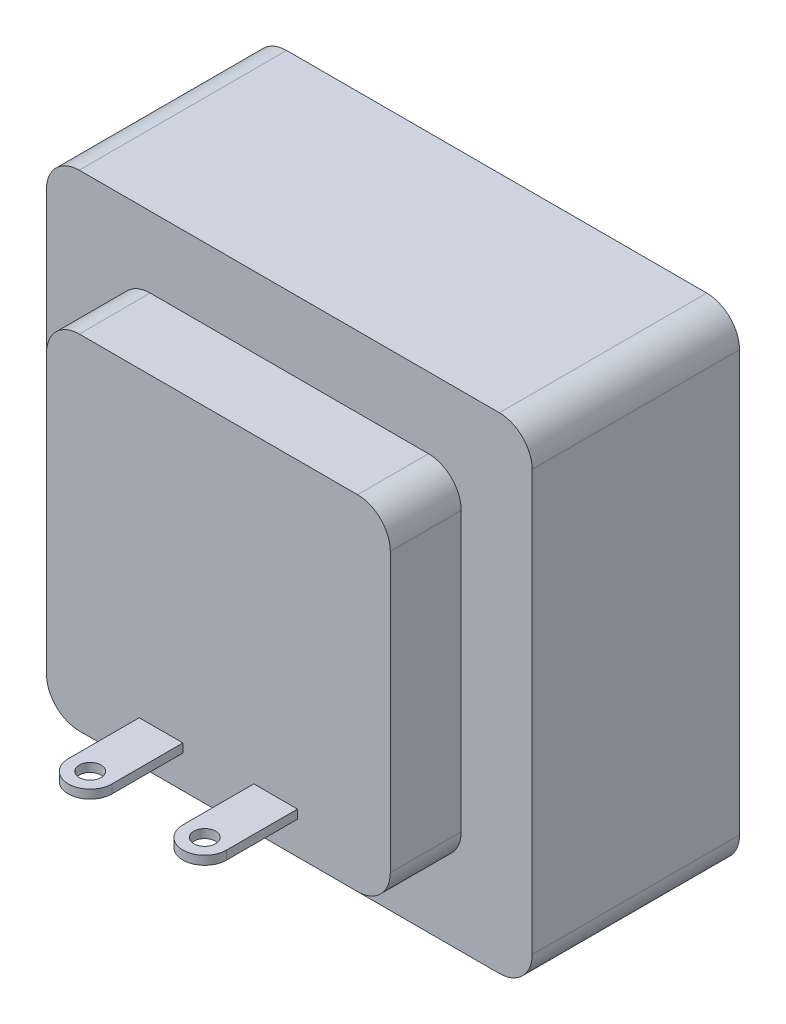
SolidWorks part; units mm, degrees
ref_plane "Front" through (0, 0, 0) normal (0, 0, 1) x (1, 0, 0)
ref_plane "Top" through (0, 0, 0) normal (0, 1, 0) x (1, 0, 0)
ref_plane "Right" through (0, 0, 0) normal (1, 0, 0) x (0, 0, -1)
sketch "Sketch1" plane through (0, 0, 0) normal (0, 0, 1) x (1, 0, 0)
  line L0 (22.25, -22.25) -> (-22.25, 22.25) construction
  line L1 (-22.25, 22.25) -> (22.25, 22.25)
  line L2 (-22.25, 22.25) -> (-22.25, -22.25)
  line L3 (-22.25, -22.25) -> (22.25, -22.25)
  line L4 (22.25, 22.25) -> (22.25, -22.25)
  dimension "D1" = 44.5
  dimension "D2" = 44.5
extrude "Base-Extrude" add sketch "Sketch1" along normal mid plane 19
sketch "Sketch2" plane through (0, 0, 0) normal (1, 0, 0) x (0, 0, -1)
  line L0 (-16, -15.75) -> (16, 15.75) construction
  line L1 (-16, 15.75) -> (16, 15.75)
  line L2 (-16, 15.75) -> (-16, -15.75)
  line L3 (-16, -15.75) -> (16, -15.75)
  line L4 (16, 15.75) -> (16, -15.75)
  line L5 (-9.5, 22.25) -> (9.5, 22.25) construction
  dimension "D1" = 6.5
  dimension "D2" = 32
extrude "Boss-Extrude1" add sketch "Sketch2" along normal offset from surface 6.5 and the other way offset from surface 6.5 up to face at (22.25, 0, 0) other way up to face at (-22.25, 0, 0)
fillet "Fillet1" radius 3 12 edges at (15.75, 15.75, 12.75) (22.25, 22.25, 0) (15.75, 15.75, -12.75) (-15.75, -15.75, -12.75) (-15.75, -15.75, 12.75) (15.75, -15.75, -12.75) (15.75, -15.75, 12.75) (-15.75, 15.75, -12.75) (-22.25, 22.25, 0) (-15.75, 15.75, 12.75) (-22.25, -22.25, 0) (22.25, -22.25, 0)
sketch "Sketch3" plane through (0, 0, 16) normal (0, 0, 1) x (1, 0, 0)
  line L0 (0, 0) -> (0, -20.3808) construction
  line L1 (-7.25, -12.75) -> (-3.25, -12.75)
  line L2 (-7.25, -12.75) -> (-7.25, -11.95)
  line L3 (-7.25, -11.95) -> (-3.25, -11.95)
  line L4 (-3.25, -12.75) -> (-3.25, -11.95)
  line L5 (3.25, -12.75) -> (3.25, -11.95)
  line L6 (7.25, -11.95) -> (3.25, -11.95)
  line L7 (7.25, -12.75) -> (7.25, -11.95)
  line L8 (7.25, -12.75) -> (3.25, -12.75)
  line L9 (12.75, -15.75) -> (-12.75, -15.75) construction
  dimension "D1" = 4
  dimension "D2" = 6.5
  dimension "D3" = 0.8
  dimension "D4" = 3
extrude "Boss-Extrude2" add sketch "Sketch3" along normal blind 6.5
sketch "Sketch4" plane through (0, -11.95, 0) normal (0, 1, 0) x (-1, 0, 0)
  line L0 (-7.25, 22.5) -> (-3.25, 22.5) construction
  line L1 (3.25, 22.5) -> (7.25, 22.5) construction
  line L2 (-7.25, 22.5) -> (-3.25, 22.5)
  line L3 (3.25, 22.5) -> (7.25, 22.5)
  arc A0 (-3.25, 22.5) -> (-7.25, 22.5) centre (-5.25, 22.5) ccw
  arc A1 (7.25, 22.5) -> (3.25, 22.5) centre (5.25, 22.5) ccw
extrude "Boss-Extrude3" add sketch "Sketch4" against normal up to surface (0.8 mm away) up to face at (5.25, -12.75, 19.25)
sketch "Sketch5" plane through (0, -11.95, 0) normal (0, 1, 0) x (-1, 0, 0)
  circle A0 centre (5.25, 22.5) radius 1
  circle A1 centre (-5.25, 22.5) radius 1
  dimension "D1" = 2
extrude "Cut-Extrude1" cut sketch "Sketch5" against normal through all
sketch "Sketch6" plane through (0, 0, 16) normal (0, 0, 1) x (1, 0, 0)
  line L0 (12.75, -15.75) -> (-12.75, -15.75) construction
  line L1 (15.75, 12.75) -> (15.75, -12.75) construction
  point P0 (9.25, -3.25)
  dimension "D1" = 12.5
  dimension "D2" = 6.5
